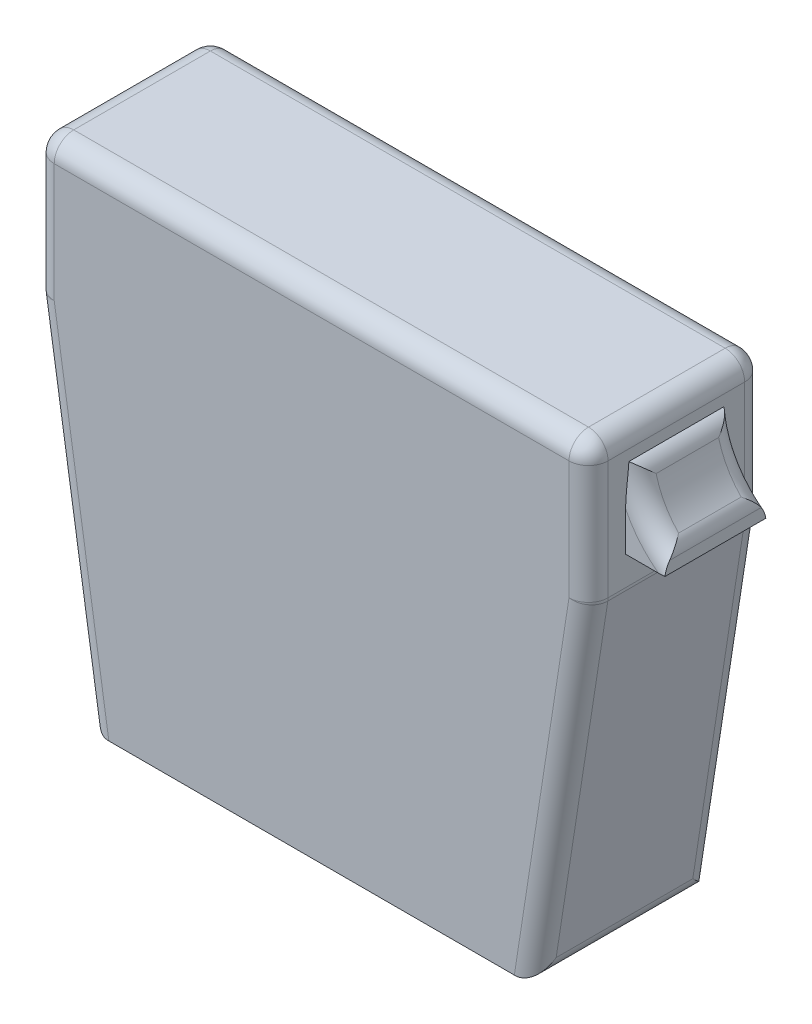
SolidWorks part; units mm, degrees
ref_plane "Front Plane" through (0, 0, 0) normal (0, 0, 1) x (1, 0, 0)
ref_plane "Top Plane" through (0, 0, 0) normal (0, 1, 0) x (1, 0, 0)
ref_plane "Right Plane" through (0, 0, 0) normal (1, 0, 0) x (0, 0, -1)
sketch "Sketch1" plane through (0, 0, 0) normal (0, 0, 1) x (1, 0, 0)
  line L0 (0, 46.0572) -> (0, -94.5693) construction
  line L1 (-98.167, 0) -> (89.088, 0) construction
  line L2 (-70.9299, 31.4929) -> (-70.9299, -4.2558)
  line L3 (-70.9299, -4.2558) -> (-56.9906, -94.5693)
  line L4 (-56.9906, -94.5693) -> (56.9906, -94.5693)
  line L5 (56.9906, -94.5693) -> (70.9299, -4.2558)
  line L6 (70.9299, -4.2558) -> (70.9299, 31.4929)
  line L7 (70.9299, 31.4929) -> (-70.9299, 31.4929)
  point P10 (0, 0)
  point P12 (-56.9906, -94.5693)
extrude "Boss-Extrude1" add sketch "Sketch1" along normal blind 45
sketch "Sketch2" plane through (70.9299, 0, 0) normal (1, 0, 0) x (0, 0, -1)
  line L0 (-22.5, 31.4929) -> (-22.5, -4.2558) construction
  line L1 (-45, 31.4929) -> (0, 31.4929) construction
  line L2 (-45, -4.2558) -> (0, -4.2558) construction
  line L3 (-45, 13.6185) -> (0, 13.6185) construction
  line L4 (-45, -4.2558) -> (-45, 31.4929) construction
  line L5 (0, -4.2558) -> (0, 31.4929) construction
  line L7 (-9.4969, 3.5555) -> (-35.5031, 3.5555)
  line L8 (-9.4969, 3.5555) -> (-9.4969, 23.6816)
  line L9 (-9.4969, 23.6816) -> (-35.5031, 23.6816)
  line L10 (-35.5031, 3.5555) -> (-35.5031, 23.6816)
  line L11 (-9.4969, 3.5555) -> (-35.5031, 23.6816) construction
  line L12 (-9.4969, 23.6816) -> (-35.5031, 3.5555) construction
  point P12 (-22.5, 13.6185)
extrude "Boss-Extrude2" add sketch "Sketch2" along normal blind 10
sketch "Sketch3" plane through (0, 0, 35.5031) normal (0, 0, 1) x (1, 0, 0)
  circle A0 centre (95.9634, 25.9857) radius 22.9202
  point P2 (95.9634, 25.9857)
extrude "Cut-Extrude1" cut sketch "Sketch3" against normal blind 33
fillet "Fillet1" radius 5 16 edges at (70.9299, -4.2558, 22.5) (-70.9299, -4.2558, 22.5) (-56.9906, -94.5693, 22.5) (56.9906, -94.5693, 22.5) (-70.9299, 31.4929, 22.5) (70.9299, 31.4929, 22.5) (0, 31.4929, 45) (0, 31.4929, 0) (-63.9602, -49.4125, 0) (-70.9299, 13.6185, 0) (70.9299, 13.6185, 0) (63.9602, -49.4125, 0) (63.9602, -49.4125, 45) (70.9299, 13.6185, 45) (-63.9602, -49.4125, 45) (-70.9299, 13.6185, 45)
fillet "Fillet2" radius 5 4 edges at (80.9299, 8.6845, 22.5) (73.1593, 23.6816, 22.5) (75.6127, 15.4412, 9.4969) (75.6127, 15.4412, 35.5031)
